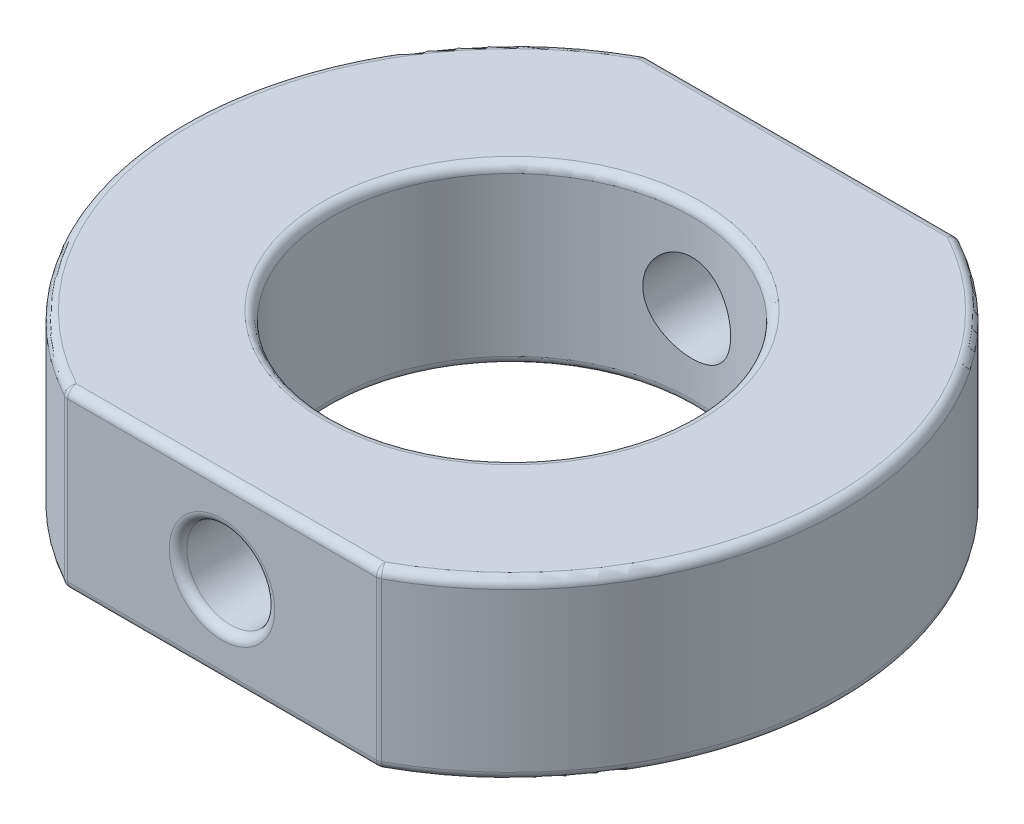
SolidWorks part; units mm, degrees
ref_plane "前视基准面" through (0, 0, 0) normal (0, 0, 1) x (1, 0, 0)
ref_plane "上视基准面" through (0, 0, 0) normal (0, 1, 0) x (1, 0, 0)
ref_plane "右视基准面" through (0, 0, 0) normal (1, 0, 0) x (0, 0, -1)
sketch "草图1" plane through (0, 0, 0) normal (0, 1, 0) x (1, 0, 0)
  circle A0 centre (0, 0) radius 7.5
  circle A1 centre (0, 0) radius 4.1
  dimension "D1" = 8.2
  dimension "D2" = 15
extrude "凸台-拉伸1" add sketch "草图1" along normal blind 2 and the other way blind 2
sketch "草图2" plane through (0, 0, 0) normal (0, 0, 1) x (1, 0, 0)
  circle A0 centre (0, 0) radius 1
  dimension "D1" = 2
extrude "切除-拉伸1" cut sketch "草图2" against normal through all and the other way through all
sketch "草图3" plane through (0, 2, 0) normal (0, 1, 0) x (1, 0, 0)
  line L0 (-1000, 0) -> (49000, 0) construction
  line L1 (-12.8534, 6.6) -> (12.8534, 6.6)
  line L2 (-12.8534, 6.6) -> (-12.8534, 9.4065)
  line L3 (-12.8534, 9.4065) -> (12.8534, 9.4065)
  line L4 (12.8534, 6.6) -> (12.8534, 9.4065)
  line L5 (0, 9.4065) -> (0, 6.6) construction
  line L6 (-12.8534, 8.0033) -> (12.8534, 8.0033) construction
  line L7 (-12.8534, -9.4065) -> (12.8534, -9.4065)
  line L8 (12.8534, -6.6) -> (12.8534, -9.4065)
  line L9 (-12.8534, -6.6) -> (12.8534, -6.6)
  line L10 (-12.8534, -6.6) -> (-12.8534, -9.4065)
  point P0 (0, 8.0033)
  dimension "D1" = 6.6
extrude "切除-拉伸2" cut sketch "草图3" against normal through all
fillet "圆角1" radius 0.2 16 edges at (0, 2, 4.1) (0, -2, 4.1) (7.5, 2, 0) (0, 2, 6.6) (-7.5, 2, 0) (0, 2, -6.6) (0, -2, 6.6) (7.5, -2, 0) (0, -2, -6.6) (-7.5, -2, 0) (-1, 0, 6.6) (3.5623, 0, 6.6) (-3.5623, 0, 6.6) (1, 0, -6.6) (-3.5623, 0, -6.6) (3.5623, 0, -6.6)
